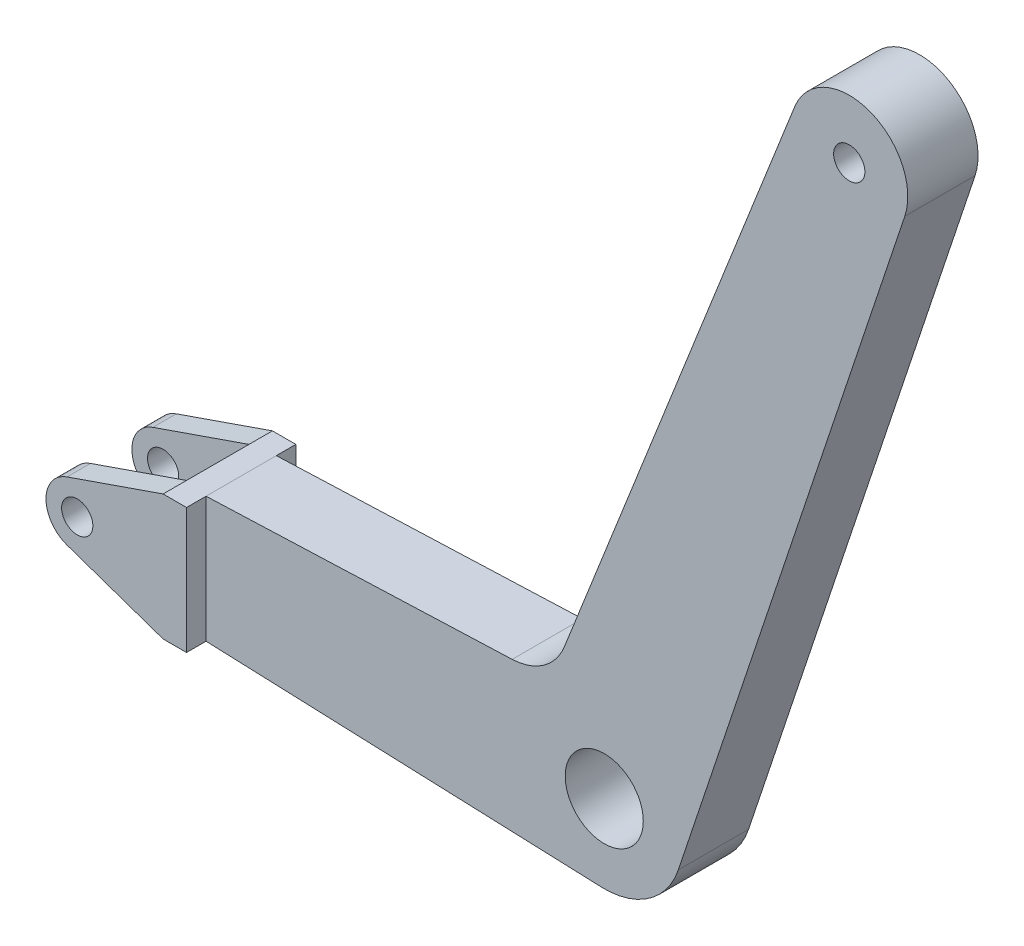
SolidWorks part; units mm, degrees
ref_plane "前视基准面" through (0, 0, 0) normal (0, 0, 1) x (1, 0, 0)
ref_plane "上视基准面" through (0, 0, 0) normal (0, 1, 0) x (1, 0, 0)
ref_plane "右视基准面" through (0, 0, 0) normal (1, 0, 0) x (0, 0, -1)
other "Configuration Table"
sketch "草图1" plane through (0, 0, 0) normal (0, 0, 1) x (1, 0, 0)
  line L0 (-130, 0) -> (0, 0) construction
  line L1 (0, 0) -> (62.7607, 172.4336) construction
  line L2 (48.8103, 177.9461) -> (-10.2101, 28.5835)
  line L3 (-23.5835, 19.1071) -> (-130.5769, 14.9889)
  line L4 (-0.7692, -19.9852) -> (-130.5769, -14.9889)
  line L5 (18.9733, -6.3258) -> (76.9906, 167.6893)
  arc A0 (-0.7692, -19.9852) -> (18.9733, -6.3258) centre (0, 0) ccw
  arc A1 (-130.5769, 14.9889) -> (-130.5769, -14.9889) centre (-130, 0) ccw
  arc A2 (76.9906, 167.6893) -> (48.8103, 177.9461) centre (62.7607, 172.4336) ccw
  arc A3 (-23.5835, 19.1071) -> (-10.2101, 28.5835) centre (-24.1604, 34.096) ccw
  dimension "D1" = 15
extrude "凸台-拉伸1" add sketch "草图1" along normal blind 18
sketch "草图2" plane through (0, 0, 0) normal (0, 0, 1) x (1, 0, 0)
  circle A0 centre (62.7607, 172.4336) radius 4
  circle A1 centre (0, 0) radius 10
extrude "切除-拉伸1" cut sketch "草图2" along normal blind 18
ref_plane "基准面1" through (-102, 0, 0) normal (-1, 0, 0) x (0, 0, 1)
sketch "草图4" plane through (-102, 0, 0) normal (-1, 0, 0) x (0, 0, 1)
  line L1 (-8.3052, 25.3644) -> (24.6949, 25.3644)
  line L2 (-8.3052, 25.3644) -> (-8.3052, -37.514)
  line L3 (-8.3052, -37.514) -> (24.6949, -37.514)
  line L4 (24.6949, 25.3644) -> (24.6949, -37.514)
extrude "切除-拉伸2" cut sketch "草图4" along normal blind 60
sketch "草图5" plane through (-102, 0, 0) normal (-1, 0, 0) x (0, 0, 1)
  line L3 (0, -16.0888) -> (18, -16.0888) construction
  line L4 (9, -16.0888) -> (-5, -16.0888)
  line L5 (9, -16.0888) -> (23, -16.0888)
  line L7 (18, 16.0888) -> (0, 16.0888) construction
  line L8 (9, 16.0888) -> (-5, 16.0888)
  line L9 (9, 16.0888) -> (23, 16.0888)
  line L10 (-5, 16.0888) -> (-5, -16.0888)
  line L11 (23, 16.0888) -> (23, -16.0888)
extrude "凸台-拉伸2" add sketch "草图5" along normal blind 6
sketch "草图6" plane through (0, 0, 0) normal (0, 0, 1) x (1, 0, 0)
  line L0 (-108, 16.0888) -> (-132.619, 7.5593)
  line L1 (-108, -16.0888) -> (-132.619, -7.5593)
  line L2 (-108, 16.0888) -> (-108, -16.0888)
  arc A0 (-132.619, 7.5593) -> (-132.619, -7.5593) centre (-130, 0) ccw
  point P0 (-130, 0)
extrude "凸台-拉伸3" add sketch "草图6" along normal blind 6 from offset 5 offset against normal yes
extrude "凸台-拉伸4" add sketch "草图6<2>" along normal blind 6 from offset 17
sketch "草图6<2>" plane through (0, 0, 0) normal (0, 0, 1) x (1, 0, 0) same geometry as "草图6"
sketch "草图7" plane through (0, 0, 0) normal (0, 0, 1) x (1, 0, 0)
  circle A0 centre (-130, 0) radius 4
  point P0 (-130, 0)
extrude "切除-拉伸3" cut sketch "草图7" against normal mid plane 60
